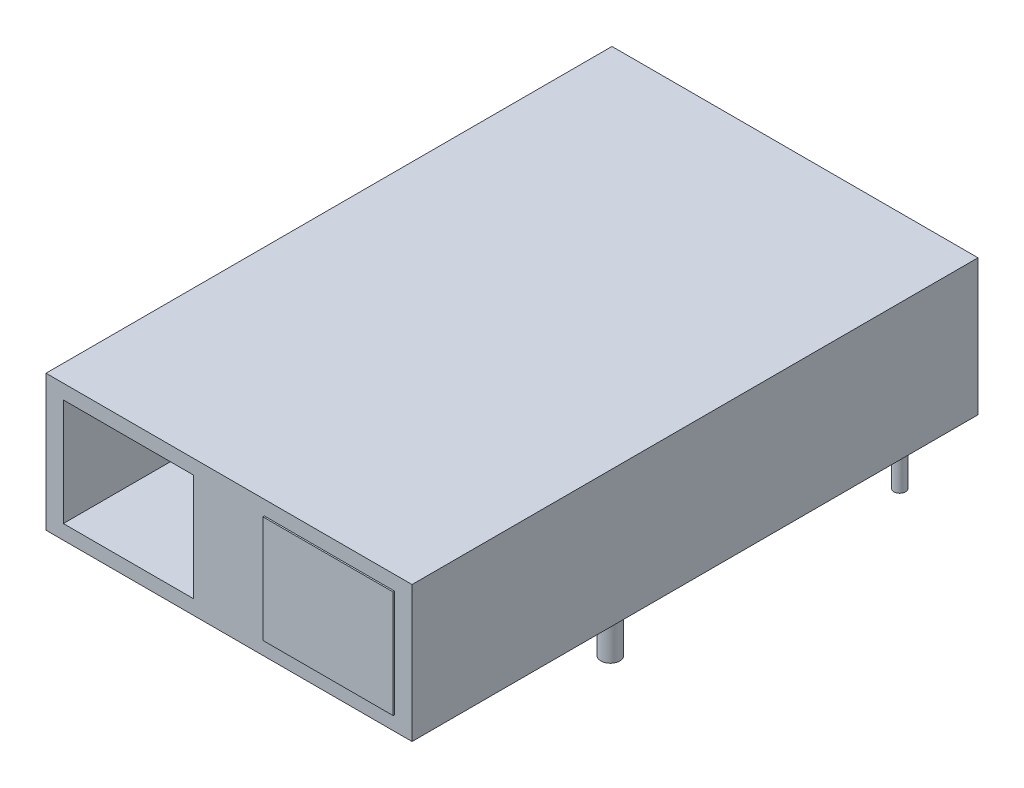
SolidWorks part; units mm, degrees
ref_plane "前视基准面" through (0, 0, 0) normal (0, 0, 1) x (1, 0, 0)
ref_plane "上视基准面" through (0, 0, 0) normal (0, 1, 0) x (1, 0, 0)
ref_plane "右视基准面" through (0, 0, 0) normal (1, 0, 0) x (0, 0, -1)
sketch "草图1" plane through (0, 0, 0) normal (0, 1, 0) x (1, 0, 0)
  line L0 (0, 44.4214) -> (0, -57.1546) construction
  line L1 (-12.65, 19.56) -> (12.65, 19.56)
  line L2 (-12.65, 19.56) -> (-12.65, -19.56)
  line L3 (-12.65, -19.56) -> (12.65, -19.56)
  line L4 (12.65, 19.56) -> (12.65, -19.56)
  line L5 (-47.0259, 0) -> (45.8683, 0) construction
  dimension "D1" = 25.3
  dimension "D2" = 39.12
extrude "凸台-拉伸1" add sketch "草图1" along normal blind 4.7 and the other way blind 4.7
sketch "草图2" plane through (0, 0, 19.56) normal (0, 0, 1) x (1, 0, 0)
  line L0 (3.3126, 0) -> (-16.9837, 0) construction
  line L1 (0, -5.5296) -> (0, 15.0399) construction
  line L3 (-11.45, 3.7) -> (-2.45, 3.7)
  line L4 (-11.45, 3.7) -> (-11.45, -3.7)
  line L5 (-11.45, -3.7) -> (-2.45, -3.7)
  line L6 (-2.45, 3.7) -> (-2.45, -3.7)
  line L8 (-12.65, -4.7) -> (-12.65, 4.7) construction
  dimension "D2" = 1.2
  dimension "D1" = 7.4
  dimension "D3" = 9
sketch "草图3" plane through (0, 0, 19.56) normal (0, 0, 1) x (1, 0, 0)
  line L0 (-1.674, 0) -> (16.4055, 0) construction
  line L1 (12.65, -4.7) -> (12.65, 4.7) construction
  line L2 (2.45, 3.7) -> (11.45, 3.7)
  line L3 (2.45, 3.7) -> (2.45, -3.7)
  line L4 (2.45, -3.7) -> (11.45, -3.7)
  line L5 (11.45, 3.7) -> (11.45, -3.7)
  dimension "D1" = 1.2
  dimension "D2" = 9
  dimension "D3" = 7.4
extrude "切除-拉伸2" cut sketch "草图2" against normal blind 10
extrude "凸台-拉伸4" add sketch "草图3" along normal blind 0.1
sketch "草图4" plane through (0, -4.7, 0) normal (0, -1, 0) x (1, 0, 0)
  line L0 (0, -16.9421) -> (0, 22.7553) construction
  line L1 (-12.65, 19.56) -> (12.65, 19.56) construction
  line L4 (-21.8184, -16.64) -> (16.1038, -16.64) construction
  circle A0 centre (-10.16, 3.36) radius 0.65
  circle A1 centre (10.16, 3.36) radius 0.65
  circle A2 centre (-10.16, -16.64) radius 0.4
  circle A3 centre (-7.62, -16.64) radius 0.4
  circle A4 centre (-5.08, -16.64) radius 0.4
  circle A5 centre (-2.54, -16.64) radius 0.4
  circle A6 centre (0, -16.64) radius 0.4
  circle A7 centre (2.54, -16.64) radius 0.4
  circle A8 centre (5.08, -16.64) radius 0.4
  circle A9 centre (7.62, -16.64) radius 0.4
  circle A10 centre (10.16, -16.64) radius 0.4
  dimension "D3" = 1.3
  dimension "D5" = 0.8
  dimension "D1" = 20.32
  dimension "D2" = 36.2
  dimension "D4" = 20
  dimension "D6" = 9
extrude "凸台-拉伸3" add sketch "草图4" along normal blind 4.2
